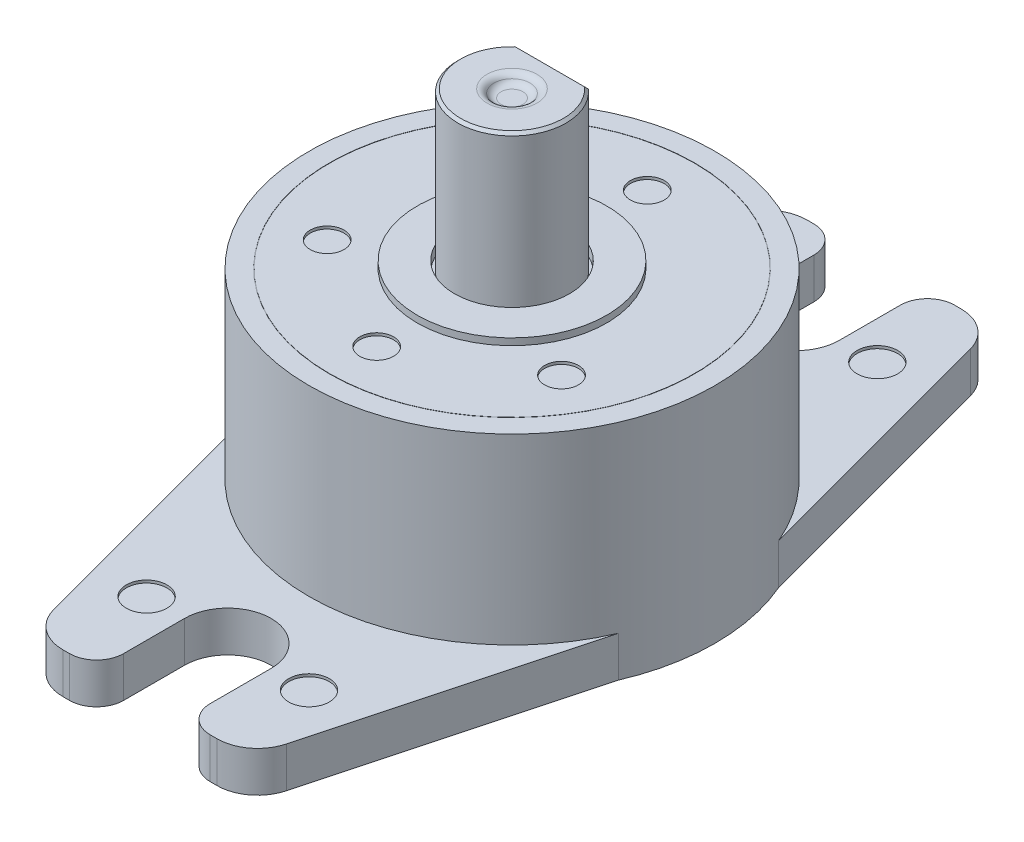
SolidWorks part; units mm, degrees
ref_plane "Front Plane" through (0, 0, 0) normal (0, 0, 1) x (1, 0, 0)
ref_plane "Top Plane" through (0, 0, 0) normal (0, 1, 0) x (1, 0, 0)
ref_plane "Right Plane" through (0, 0, 0) normal (1, 0, 0) x (0, 0, -1)
sketch "Sketch1" plane through (0, 0, 0) normal (1, 0, 0) x (0, 0, -1)
  line L0 (0, -7) -> (0, 7) construction
  line L2 (-13.75, -5.5) -> (13.75, -5.5)
  line L3 (-13.75, -5.5) -> (-13.75, -7)
  line L4 (-13.75, -7) -> (13.75, -7)
  line L5 (13.75, -5.5) -> (13.75, -7)
  line L6 (-13.75, -5.5) -> (13.75, -7) construction
  line L7 (-13.75, -7) -> (13.75, -5.5) construction
  line L8 (-7.5, 1.5) -> (7.5, 1.5)
  line L9 (-7.5, 1.5) -> (-7.5, -5.5)
  line L10 (-7.5, -5.5) -> (7.5, -5.5)
  line L11 (7.5, 1.5) -> (7.5, -5.5)
  line L12 (-7.5, 1.5) -> (7.5, -5.5) construction
  line L13 (-7.5, -5.5) -> (7.5, 1.5) construction
  line L14 (-2, 7) -> (2, 7)
  line L15 (-2, 7) -> (-2, 1.5)
  line L16 (-2, 1.5) -> (2, 1.5)
  line L17 (2, 7) -> (2, 1.5)
  line L18 (-2, 7) -> (2, 1.5) construction
  line L19 (-2, 1.5) -> (2, 7) construction
  line L20 (-5.2, 7) -> (5.2, 7)
  line L21 (-4.4, 7) -> (4.4, 7)
  point P0 (0, -6.25)
  point P3 (0, 4.25)
  point P4 (0, 0)
  point P11 (0, -2)
  point P19 (0, 2.5)
  point P26 (0, 7)
  point P29 (0, 7)
  dimension "D1" = 7
  dimension "D2" = 1.5
  dimension "Overall Height" = 14
  dimension "D4" = 10.4
  dimension "Overall Length" = 27.5
  dimension "Overall Width" = 15
  dimension "Shaft Diameter" = 4
  dimension "D12" = 5.5
  dimension "Shaft Length" = 4.5
  dimension "Gear Pitch Diameter" = 8.8
sketch "Sketch2" plane through (0, 0, 0) normal (0, 1, 0) x (1, 0, 0)
  line L0 (0, -10.5) -> (0, 10.5) construction
  line L6 (-1.6, -10.5) -> (-1.6, -13.75)
  line L10 (-1.6, -13.75) -> (-4, -13.75)
  line L11 (-4, -13.75) -> (-6.8912, -2.9601)
  line L14 (-1.3229, 1.5) -> (1.3229, 1.5)
  line L17 (1.6, -10.5) -> (1.6, -13.75)
  line L18 (1.6, -13.75) -> (4, -13.75)
  line L19 (4, -13.75) -> (6.8912, -2.9601)
  line L20 (-7.5, 0) -> (7.5, 0) construction
  line L21 (4, 13.75) -> (6.8912, 2.9601)
  line L22 (1.6, 13.75) -> (4, 13.75)
  line L23 (1.6, 10.5) -> (1.6, 13.75)
  line L24 (-1.6, 10.5) -> (-1.6, 13.75)
  line L25 (-1.6, 13.75) -> (-4, 13.75)
  line L26 (-4, 13.75) -> (-6.8912, 2.9601)
  circle A0 centre (0, 0) radius 7.5
  circle A4 centre (0, 0) radius 2
  circle A5 centre (0, -10.5) radius 1.6
  circle A6 centre (0, 10.5) radius 1.6
  circle A7 centre (0, 0) radius 4.4
  point P8 (0, -2)
  point P14 (0, 0)
  point P23 (0, 0)
  dimension "D4" = 8
  dimension "Mounting Hole Diameter" = 3.2
  dimension "D5" = 30
  dimension "Mounting Hole Center to Center" = 21
  dimension "Shaft Width" = 3.5
ref_plane "Plane1" through (0, -7, -13.75) normal (0, -1, 0) x (-1, 0, 0)
sketch "Sketch3" plane through (0, -7, -13.75) normal (0, -1, 0) x (-1, 0, 0)
  line L0 (4, -27.5) -> (6.8912, -16.7101) construction
  line L5 (1.6, -27.5) -> (4, -27.5) construction
  line L6 (1.6, -24.25) -> (1.6, -27.5) construction
  line L7 (-1.6, -24.25) -> (-1.6, -27.5) construction
  line L8 (-1.6, -27.5) -> (-4, -27.5) construction
  line L9 (-4, -27.5) -> (-6.8912, -16.7101) construction
  line L10 (-4, 0) -> (-6.8912, -10.7899) construction
  line L11 (-1.6, 0) -> (-4, 0) construction
  line L12 (-1.6, -3.25) -> (-1.6, 0) construction
  line L13 (1.6, -3.25) -> (1.6, 0) construction
  line L14 (1.6, 0) -> (4, 0) construction
  line L15 (4, 0) -> (6.8912, -10.7899) construction
  line L16 (4, -27.5) -> (6.8912, -16.7101)
  line L17 (1.6, -27.5) -> (4, -27.5)
  line L18 (1.6, -24.25) -> (1.6, -27.5)
  line L19 (-1.6, -24.25) -> (-1.6, -27.5)
  line L20 (-1.6, -27.5) -> (-4, -27.5)
  line L21 (-4, -27.5) -> (-6.8912, -16.7101)
  line L22 (-4, 0) -> (-6.8912, -10.7899)
  line L23 (-1.6, 0) -> (-4, 0)
  line L24 (-1.6, -3.25) -> (-1.6, 0)
  line L25 (1.6, -3.25) -> (1.6, 0)
  line L26 (1.6, 0) -> (4, 0)
  line L27 (4, 0) -> (6.8912, -10.7899)
  circle A4 centre (0, -13.75) radius 7.5
  circle A5 centre (0, -13.75) radius 7.5 construction
  circle A6 centre (0, -24.25) radius 1.6 construction
  circle A7 centre (0, -3.25) radius 1.6 construction
  circle A8 centre (0, -24.25) radius 1.6
  circle A9 centre (0, -3.25) radius 1.6
extrude "Boss-Extrude1" add sketch "Sketch3" against normal up to vertex (1.5 mm away) contours A8 L18 L17 L16 A4 L21 L20 L19 | A4 | A9 L24 L23 L22 A4 L27 L26 L25 region at (-2.8, -7, 13.575) region at (0, -7, 0) region at (5.2765, -7, -8.3097) up to point (0, -5.5, -13.75)
sketch "Sketch12" plane through (0, -5.5, 0) normal (0, 1, 0) x (1, 0, 0)
  circle A0 centre (0, 0) radius 7.5
  circle A1 centre (0, 0) radius 7.5 construction
extrude "Boss-Extrude3" add sketch "Sketch12" along normal up to vertex (7 mm away) up to point (0, 1.5, -7.5)
sketch "Sketch6" plane through (0, 0, 0) normal (1, 0, 0) x (0, 0, -1)
  line L8 (0, -6.625) -> (-7.125, -6.625)
  line L10 (-7.125, -6.625) -> (-7.125, 1.125)
  line L12 (-7.125, 1.125) -> (-2.125, 1.125)
  line L13 (-2.125, 1.125) -> (-2.125, 1.5)
  line L14 (-7.5, 1.5) -> (7.5, 1.5) construction
  line L15 (-2.125, 1.5) -> (0, 1.5)
  line L16 (0, 1.5) -> (0, -6.625)
  line L17 (-13.75, -7) -> (13.75, -7) construction
  line L18 (-7.5, 1.5) -> (-7.5, -5.5) construction
  line L19 (-2, 7) -> (-2, 1.5) construction
  dimension "D1" = 0.375
  dimension "D2" = 0.375
  dimension "D3" = 0.125
  dimension "D4" = 0.375
revolve "Cut-Revolve1" cut sketch "Sketch6" angle 360 about L16 region at (0, -2.6922, 3.5269)
sketch "Sketch7" plane through (0, 0, 0) normal (1, 0, 0) x (0, 0, -1)
  line L7 (0, 7) -> (0, -6.625)
  line L8 (-2, 7) -> (2, 7) construction
  line L9 (0, -6.625) -> (-7.125, -6.625)
  line L10 (-7.125, -6.625) -> (-7.125, 1.125)
  line L11 (-7.125, 1.125) -> (-2, 1.125)
  line L13 (-2, 1.125) -> (-2, 7)
  line L14 (-2, 7) -> (0, 7)
revolve "Revolve1" add sketch "Sketch7" angle 360 about L7
sketch "Sketch8" plane through (0, 7, 0) normal (0, 1, 0) x (1, 0, 0)
  line L1 (-1.3229, 1.5) -> (1.3229, 1.5)
  line L2 (0, -13.75) -> (0, 13.75) construction
  circle A0 centre (0, 0) radius 2
  circle A1 centre (0, 0) radius 2 construction
extrude "Cut-Extrude2" cut sketch "Sketch8" against normal up to vertex (4.5 mm away) contours L1 region at (0, 7, -1.7023) up to point (0, 2.5, 0)
chamfer "Chamfer1" distance 0.1 angle 45 2 edges at (0, 7, 2) (0, 7, -1.5)
sketch "Sketch9" plane through (0, 1.5, 0) normal (0, 1, 0) x (1, 0, 0)
  line L0 (-7.5, 0) -> (7.5, 0) construction
  circle A0 centre (0, 0) radius 7.5
  circle A1 centre (0, 0) radius 3.5
  circle A2 centre (0, 0) radius 7.5 construction
  dimension "D2" = 7
extrude "Cut-Extrude3" cut sketch "Sketch9" against normal blind 0.25 contours A0 A1 region at (-7.2879, 1.5, 0)
sketch "Sketch13" plane through (0, 1.25, 0) normal (0, 1, 0) x (1, 0, 0)
  line L0 (0, -13.75) -> (0, 13.75) construction
  circle A0 centre (0, 5) radius 0.625
  circle A1 centre (0, 0) radius 5 construction
  circle A2 centre (4.3301, -2.5) radius 0.625
  circle A3 centre (-4.3301, -2.5) radius 0.625
  circle A4 centre (0, -5) radius 0.625
  point P13 (0, 0)
  dimension "D1" = 10
  dimension "D2" = 1.25
  dimension "D3" = 3
extrude "Cut-Extrude6" cut sketch "Sketch13" against normal blind 0.1
fillet "Fillet3" radius 1.5 4 edges at (4, -6.25, -13.75) (-4, -6.25, -13.75) (4, -6.25, 13.75) (-4, -6.25, 13.75)
fillet "Fillet4" radius 1 4 edges at (-1.6, -6.25, 13.75) (1.6, -6.25, 13.75) (-1.6, -6.25, -13.75) (1.6, -6.25, -13.75)
sketch "Sketch10" plane through (0, 7, 0) normal (0, 1, 0) x (1, 0, 0)
  circle A0 centre (0, 0) radius 0.75
  circle A1 centre (0, 0) radius 3.5 construction
  dimension "D1" = 1.5
extrude "Cut-Extrude4" cut sketch "Sketch10" against normal blind 0.3 draft 30
sketch "Sketch15" plane through (0, 1.25, 0) normal (0, 1, 0) x (1, 0, 0)
  circle A2 centre (0, 0) radius 6.74
  circle A3 centre (0, 0) radius 6.75
  circle A4 centre (0, 0) radius 6.75
  dimension "D1" = 0.75
  dimension "D2" = 0.01
extrude "Cut-Extrude7" cut sketch "Sketch15" against normal blind 0.01
fillet "Fillet2" radius 0.3 2 edges at (0, 6.7, 0.5768) (0, 7, 0.75)
sketch "Sketch11" plane through (0, -5.5, 0) normal (0, 1, 0) x (1, 0, 0)
  line L0 (-3, -10.5) -> (3, -10.5) construction
  line L2 (-3, 10.5) -> (3, 10.5) construction
  circle A0 centre (3, 10.5) radius 0.75
  circle A1 centre (-3, 10.5) radius 0.75
  circle A2 centre (3, -10.5) radius 0.75
  circle A3 centre (-3, -10.5) radius 0.75
  point P4 (0, -10.5)
  point P9 (0, 10.5)
  dimension "D1" = 1.5
  dimension "D2" = 6
extrude "Cut-Extrude5" cut sketch "Sketch11" against normal blind 0.1
sketch "Sketch14" plane through (0, 7, 0) normal (0, 1, 0) x (1, 0, 0)
  line L0 (-1.3229, 1.5) -> (1.3229, 1.5)
  line L1 (0, 3.6) -> (0, 5.2) construction
  arc A0 (-1.3229, 1.5) -> (1.3229, 1.5) centre (0, 0) ccw
  arc A1 (-1.3229, 1.5) -> (1.3229, 1.5) centre (0, 0) ccw construction
  circle A2 centre (0, 0) radius 3.6
  circle A3 centre (0, 0) radius 5.2
  arc A4 (-0.5625, 3.5558) -> (-0.3, 5.1913) centre (2.9264, 3.8347) cw
  arc A5 (0.5625, 3.5558) -> (0.3, 5.1913) centre (-2.9264, 3.8347) ccw
  arc A6 (1.4492, 3.2954) -> (2.5543, 4.5294) centre (4.535, 1.6438) cw
  arc A7 (2.3956, 2.6872) -> (3.059, 4.205) centre (-0.3886, 4.8081) ccw
  arc A8 (3.0008, 1.9888) -> (4.5976, 2.4294) centre (4.7038, -1.0689) cw
  arc A9 (3.4681, 0.9655) -> (4.8468, 1.8837) centre (2.2725, 4.2549) ccw
  arc A10 (3.5996, 0.0507) -> (5.1812, -0.4419) centre (3.3792, -3.4423) cw
  arc A11 (3.4395, -1.0628) -> (5.0958, -1.0358) centre (4.2121, 2.3509) ccw
  arc A12 (3.0556, -1.9034) -> (4.1198, -3.1729) centre (0.9817, -4.7228) cw
  arc A13 (2.3189, -2.7537) -> (3.7269, -3.6263) centre (4.8144, -0.2996) ccw
  arc A14 (1.5415, -3.2533) -> (1.7504, -4.8965) centre (-1.7275, -4.5038) cw
  arc A15 (0.4621, -3.5702) -> (1.1747, -5.0656) centre (3.8882, -2.8549) ccw
  arc A16 (-0.4621, -3.5702) -> (-1.1747, -5.0656) centre (-3.8882, -2.8549) cw
  arc A17 (-1.5415, -3.2533) -> (-1.7504, -4.8965) centre (1.7275, -4.5038) ccw
  arc A18 (-2.3189, -2.7537) -> (-3.7269, -3.6263) centre (-4.8144, -0.2996) cw
  arc A19 (-3.0556, -1.9034) -> (-4.1198, -3.1729) centre (-0.9817, -4.7228) ccw
  arc A20 (-3.4395, -1.0628) -> (-5.0958, -1.0358) centre (-4.2121, 2.3509) cw
  arc A21 (-3.5996, 0.0507) -> (-5.1812, -0.4419) centre (-3.3792, -3.4423) ccw
  arc A22 (-3.4681, 0.9655) -> (-4.8468, 1.8837) centre (-2.2725, 4.2549) cw
  arc A23 (-3.0008, 1.9888) -> (-4.5976, 2.4294) centre (-4.7038, -1.0689) ccw
  arc A24 (-2.3956, 2.6872) -> (-3.059, 4.205) centre (0.3886, 4.8081) cw
  arc A25 (-1.4492, 3.2954) -> (-2.5543, 4.5294) centre (-4.535, 1.6438) ccw
  point P18 (0, 4.4)
  point P79 (0, 0)
  dimension "D2" = 0.6
  dimension "D4" = 3.5
  dimension "D3" = 1.125
sketch "Sketch16" plane through (0, 0, 0) normal (1, 0, 0) x (0, 0, -1)
  line L0 (0, -7) -> (0, -6.9)
  line L1 (-2.9601, -7) -> (2.9601, -7) construction
  line L2 (0, -7) -> (-0.5, -7)
  line L3 (-0.5, -7) -> (-0.5, -6.9) construction
  line L4 (-0.5, -6.9) -> (0, -6.9) construction
  arc A0 (-0.5, -7) -> (0, -6.9) centre (0, -8.2) cw
  dimension "D1" = 0.5
  dimension "D2" = 0.1
revolve "Cut-Revolve2" cut sketch "Sketch16" angle 360 about L0
equation "\".25mmm\"=6.35"
